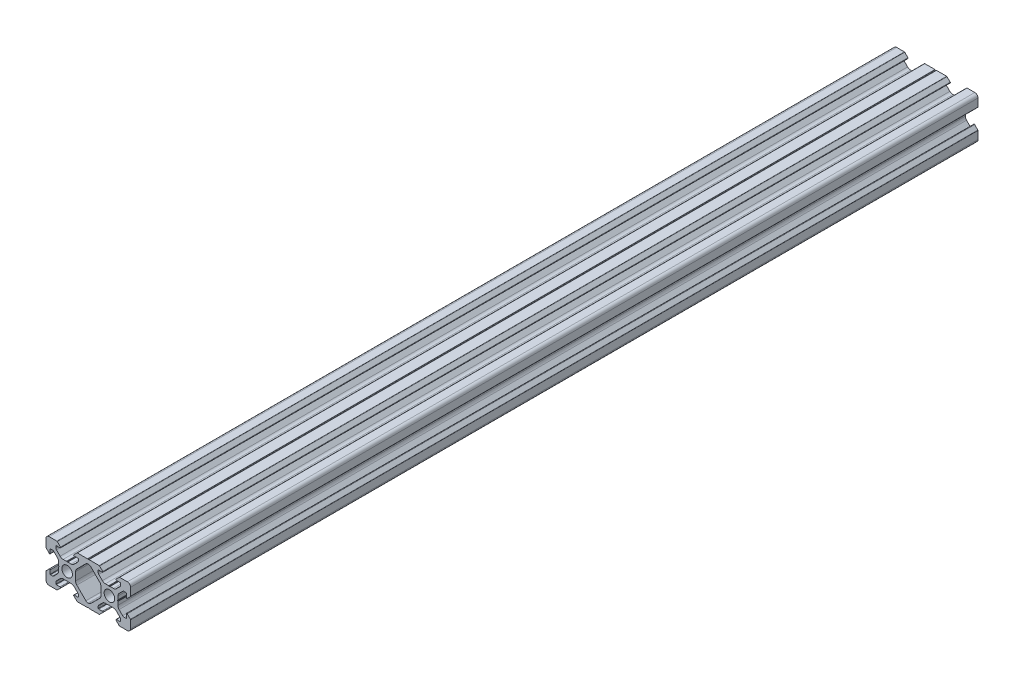
SolidWorks part; units mm, degrees
material "6063-T5"
ref_plane "Спереди" through (0, 0, 0) normal (0, 0, 1) x (1, 0, 0)
ref_plane "Сверху" through (0, 0, 0) normal (0, 1, 0) x (1, 0, 0)
ref_plane "Справа" through (0, 0, 0) normal (1, 0, 0) x (0, 0, -1)
sketch "Model" plane through (0, 0, 0) normal (0, 0, 1) x (1, 0, 0)
  line L0 (-5.4142, 2.9753) -> (-1.1373, 7.2523)
  line L1 (-6, -2.2365) -> (-6, 1.5611)
  line L2 (-5.4142, -3.6507) -> (-1.1373, -7.9276)
  line L3 (-0.1473, -8.3377) -> (0.1473, -8.3377)
  line L4 (5.4142, -3.6507) -> (1.1373, -7.9276)
  line L5 (6, -2.2365) -> (6, 1.5611)
  line L6 (5.4142, 2.9753) -> (1.1373, 7.2523)
  line L7 (-0.1473, 7.6623) -> (0.1473, 7.6623)
  line L8 (0.3757, 9.6623) -> (5.17, 9.6623)
  line L9 (5.3468, 9.5891) -> (6.8468, 8.0891)
  line L10 (6.67, 7.6623) -> (4.9, 7.6623)
  line L11 (4.7, 7.4623) -> (4.7, 6.6493)
  line L12 (4.9929, 5.9422) -> (6.687, 4.2481)
  line L13 (8.1012, 3.6623) -> (9.6623, 3.6623)
  line L14 (9.8185, 3.6075) -> (10, 3.4623)
  line L15 (10.1815, 3.6075) -> (10, 3.4623)
  line L16 (13.313, 4.2481) -> (15.0071, 5.9422)
  line L17 (15.3, 6.6493) -> (15.3, 7.4623)
  line L18 (15.1, 7.6623) -> (13.33, 7.6623)
  line L19 (14.6532, 9.5891) -> (13.1532, 8.0891)
  line L20 (14.83, 9.6623) -> (18.5, 9.6623)
  line L21 (20, 4.4923) -> (20, 8.1623)
  line L22 (19.9268, 4.3155) -> (18.4268, 2.8155)
  line L23 (18, 4.7623) -> (18, 2.9923)
  line L24 (16.987, 4.9623) -> (17.8, 4.9623)
  line L25 (14.5858, 2.9753) -> (16.2799, 4.6694)
  line L26 (14, 0) -> (14, 1.5611)
  line L27 (13.9452, -0.1562) -> (13.8, -0.3377)
  line L28 (13.9452, -0.5192) -> (13.8, -0.3377)
  line L29 (14, -0.6754) -> (14, -2.2365)
  line L30 (14.5858, -3.6507) -> (16.2799, -5.3448)
  line L31 (16.987, -5.6377) -> (17.8, -5.6377)
  line L32 (18, -5.4377) -> (18, -3.6677)
  line L33 (19.9268, -4.9909) -> (18.4268, -3.4909)
  line L34 (20, -5.1677) -> (20, -8.8377)
  line L35 (14.83, -10.3377) -> (18.5, -10.3377)
  line L36 (14.6532, -10.2645) -> (13.1532, -8.7645)
  line L37 (15.1, -8.3377) -> (13.33, -8.3377)
  line L38 (15.3, -7.3247) -> (15.3, -8.1377)
  line L39 (13.313, -4.9235) -> (15.0071, -6.6176)
  line L40 (10.3377, -4.3377) -> (11.8988, -4.3377)
  line L41 (10.1815, -4.2829) -> (10, -4.1377)
  line L42 (9.8185, -4.2829) -> (10, -4.1377)
  line L43 (8.1012, -4.3377) -> (9.6623, -4.3377)
  line L44 (4.9929, -6.6176) -> (6.687, -4.9235)
  line L45 (4.7, -8.1377) -> (4.7, -7.3247)
  line L46 (6.67, -8.3377) -> (4.9, -8.3377)
  line L47 (5.3468, -10.2645) -> (6.8468, -8.7645)
  line L48 (0.3757, -10.3377) -> (5.17, -10.3377)
  line L49 (0, -10.1377) -> (0.237, -10.2957)
  line L50 (0, -10.1377) -> (-0.237, -10.2957)
  line L51 (-0.3757, -10.3377) -> (-5.17, -10.3377)
  line L52 (-5.3468, -10.2645) -> (-6.8468, -8.7645)
  line L53 (-6.67, -8.3377) -> (-4.9, -8.3377)
  line L54 (-4.7, -8.1377) -> (-4.7, -7.3247)
  line L55 (-4.9929, -6.6176) -> (-6.687, -4.9235)
  line L56 (-8.1012, -4.3377) -> (-9.6623, -4.3377)
  line L57 (-9.8185, -4.2829) -> (-10, -4.1377)
  line L58 (-10.1815, -4.2829) -> (-10, -4.1377)
  line L59 (-10.3377, -4.3377) -> (-11.8988, -4.3377)
  line L60 (-13.313, -4.9235) -> (-15.0071, -6.6176)
  line L61 (-15.3, -7.3247) -> (-15.3, -8.1377)
  line L62 (-15.1, -8.3377) -> (-13.33, -8.3377)
  line L63 (-14.6532, -10.2645) -> (-13.1532, -8.7645)
  line L64 (-14.83, -10.3377) -> (-18.5, -10.3377)
  line L65 (-20, -5.1677) -> (-20, -8.8377)
  line L66 (-19.9268, -4.9909) -> (-18.4268, -3.4909)
  line L67 (-18, -5.4377) -> (-18, -3.6677)
  line L68 (-16.987, -5.6377) -> (-17.8, -5.6377)
  line L69 (-14.5858, -3.6507) -> (-16.2799, -5.3448)
  line L70 (-14, -0.6754) -> (-14, -2.2365)
  line L71 (-13.9452, -0.5192) -> (-13.8, -0.3377)
  line L72 (-13.9452, -0.1562) -> (-13.8, -0.3377)
  line L73 (-14, 0) -> (-14, 1.5611)
  line L74 (-14.5858, 2.9753) -> (-16.2799, 4.6694)
  line L75 (-16.987, 4.9623) -> (-17.8, 4.9623)
  line L76 (-18, 4.7623) -> (-18, 2.9923)
  line L77 (-19.9268, 4.3155) -> (-18.4268, 2.8155)
  line L78 (-20, 4.4923) -> (-20, 8.1623)
  line L79 (-14.6532, 9.5891) -> (-13.1532, 8.0891)
  line L80 (-10.1815, 3.6075) -> (-10, 3.4623)
  line L81 (-9.8185, 3.6075) -> (-10, 3.4623)
  line L82 (-8.1012, 3.6623) -> (-9.6623, 3.6623)
  line L83 (-4.9929, 5.9422) -> (-6.687, 4.2481)
  line L84 (-4.7, 7.4623) -> (-4.7, 6.6493)
  line L85 (-6.67, 7.6623) -> (-4.9, 7.6623)
  line L86 (-5.3468, 9.5891) -> (-6.8468, 8.0891)
  line L87 (-0.3757, 9.6623) -> (-5.17, 9.6623)
  line L88 (0, 9.4623) -> (-0.237, 9.6203)
  line L89 (0, 9.4623) -> (0.237, 9.6203)
  line L90 (10.3377, 3.6623) -> (11.8988, 3.6623)
  line L91 (-10.3377, 3.6623) -> (-11.8988, 3.6623)
  line L92 (-13.313, 4.2481) -> (-15.0071, 5.9422)
  line L93 (-15.3, 6.6493) -> (-15.3, 7.4623)
  line L94 (-15.1, 7.6623) -> (-13.33, 7.6623)
  line L95 (-14.83, 9.6623) -> (-18.5, 9.6623)
  circle A0 centre (10, -0.3377) radius 2.5
  arc A1 (-0.1473, 7.6623) -> (-1.1373, 7.2523) centre (-0.1473, 6.2623) ccw
  arc A2 (-5.4142, 2.9753) -> (-6, 1.5611) centre (-4, 1.5611) ccw
  arc A3 (-6, -2.2365) -> (-5.4142, -3.6507) centre (-4, -2.2365) ccw
  arc A4 (-1.1373, -7.9276) -> (-0.1473, -8.3377) centre (-0.1473, -6.9377) ccw
  arc A5 (0.1473, -8.3377) -> (1.1373, -7.9276) centre (0.1473, -6.9377) ccw
  arc A6 (5.4142, -3.6507) -> (6, -2.2365) centre (4, -2.2365) ccw
  arc A7 (6, 1.5611) -> (5.4142, 2.9753) centre (4, 1.5611) ccw
  arc A8 (1.1373, 7.2523) -> (0.1473, 7.6623) centre (0.1473, 6.2623) ccw
  arc A9 (0.3757, 9.6623) -> (0.237, 9.6203) centre (0.3757, 9.4123) ccw
  arc A10 (5.3468, 9.5891) -> (5.17, 9.6623) centre (5.17, 9.4123) ccw
  arc A11 (6.67, 7.6623) -> (6.8468, 8.0891) centre (6.67, 7.9123) ccw
  arc A12 (4.9, 7.6623) -> (4.7, 7.4623) centre (4.9, 7.4623) ccw
  arc A13 (4.7, 6.6493) -> (4.9929, 5.9422) centre (5.7, 6.6493) ccw
  arc A14 (6.687, 4.2481) -> (8.1012, 3.6623) centre (8.1012, 5.6623) ccw
  arc A15 (9.8185, 3.6075) -> (9.6623, 3.6623) centre (9.6623, 3.4123) ccw
  arc A16 (10.3377, 3.6623) -> (10.1815, 3.6075) centre (10.3377, 3.4123) ccw
  arc A17 (11.8988, 3.6623) -> (13.313, 4.2481) centre (11.8988, 5.6623) ccw
  arc A18 (15.0071, 5.9422) -> (15.3, 6.6493) centre (14.3, 6.6493) ccw
  arc A19 (15.3, 7.4623) -> (15.1, 7.6623) centre (15.1, 7.4623) ccw
  arc A20 (13.1532, 8.0891) -> (13.33, 7.6623) centre (13.33, 7.9123) ccw
  arc A21 (14.83, 9.6623) -> (14.6532, 9.5891) centre (14.83, 9.4123) ccw
  arc A22 (20, 8.1623) -> (18.5, 9.6623) centre (18.5, 8.1623) ccw
  arc A23 (19.9268, 4.3155) -> (20, 4.4923) centre (19.75, 4.4923) ccw
  arc A24 (18, 2.9923) -> (18.4268, 2.8155) centre (18.25, 2.9923) ccw
  arc A25 (18, 4.7623) -> (17.8, 4.9623) centre (17.8, 4.7623) ccw
  arc A26 (16.987, 4.9623) -> (16.2799, 4.6694) centre (16.987, 3.9623) ccw
  arc A27 (14.5858, 2.9753) -> (14, 1.5611) centre (16, 1.5611) ccw
  arc A28 (13.9452, -0.1562) -> (14, 0) centre (13.75, 0) ccw
  arc A29 (14, -0.6754) -> (13.9452, -0.5192) centre (13.75, -0.6754) ccw
  arc A30 (14, -2.2365) -> (14.5858, -3.6507) centre (16, -2.2365) ccw
  arc A31 (16.2799, -5.3448) -> (16.987, -5.6377) centre (16.987, -4.6377) ccw
  arc A32 (17.8, -5.6377) -> (18, -5.4377) centre (17.8, -5.4377) ccw
  arc A33 (18.4268, -3.4909) -> (18, -3.6677) centre (18.25, -3.6677) ccw
  arc A34 (20, -5.1677) -> (19.9268, -4.9909) centre (19.75, -5.1677) ccw
  arc A35 (18.5, -10.3377) -> (20, -8.8377) centre (18.5, -8.8377) ccw
  arc A36 (14.6532, -10.2645) -> (14.83, -10.3377) centre (14.83, -10.0877) ccw
  arc A37 (13.33, -8.3377) -> (13.1532, -8.7645) centre (13.33, -8.5877) ccw
  arc A38 (15.1, -8.3377) -> (15.3, -8.1377) centre (15.1, -8.1377) ccw
  arc A39 (15.3, -7.3247) -> (15.0071, -6.6176) centre (14.3, -7.3247) ccw
  arc A40 (13.313, -4.9235) -> (11.8988, -4.3377) centre (11.8988, -6.3377) ccw
  arc A41 (10.1815, -4.2829) -> (10.3377, -4.3377) centre (10.3377, -4.0877) ccw
  arc A42 (9.6623, -4.3377) -> (9.8185, -4.2829) centre (9.6623, -4.0877) ccw
  arc A43 (8.1012, -4.3377) -> (6.687, -4.9235) centre (8.1012, -6.3377) ccw
  arc A44 (4.9929, -6.6176) -> (4.7, -7.3247) centre (5.7, -7.3247) ccw
  arc A45 (4.7, -8.1377) -> (4.9, -8.3377) centre (4.9, -8.1377) ccw
  arc A46 (6.8468, -8.7645) -> (6.67, -8.3377) centre (6.67, -8.5877) ccw
  arc A47 (5.17, -10.3377) -> (5.3468, -10.2645) centre (5.17, -10.0877) ccw
  arc A48 (0.237, -10.2957) -> (0.3757, -10.3377) centre (0.3757, -10.0877) ccw
  arc A49 (-0.3757, -10.3377) -> (-0.237, -10.2957) centre (-0.3757, -10.0877) ccw
  arc A50 (-5.3468, -10.2645) -> (-5.17, -10.3377) centre (-5.17, -10.0877) ccw
  arc A51 (-6.67, -8.3377) -> (-6.8468, -8.7645) centre (-6.67, -8.5877) ccw
  arc A52 (-4.9, -8.3377) -> (-4.7, -8.1377) centre (-4.9, -8.1377) ccw
  arc A53 (-4.7, -7.3247) -> (-4.9929, -6.6176) centre (-5.7, -7.3247) ccw
  arc A54 (-6.687, -4.9235) -> (-8.1012, -4.3377) centre (-8.1012, -6.3377) ccw
  arc A55 (-9.8185, -4.2829) -> (-9.6623, -4.3377) centre (-9.6623, -4.0877) ccw
  arc A56 (-10.3377, -4.3377) -> (-10.1815, -4.2829) centre (-10.3377, -4.0877) ccw
  arc A57 (-11.8988, -4.3377) -> (-13.313, -4.9235) centre (-11.8988, -6.3377) ccw
  arc A58 (-15.0071, -6.6176) -> (-15.3, -7.3247) centre (-14.3, -7.3247) ccw
  arc A59 (-15.3, -8.1377) -> (-15.1, -8.3377) centre (-15.1, -8.1377) ccw
  arc A60 (-13.1532, -8.7645) -> (-13.33, -8.3377) centre (-13.33, -8.5877) ccw
  arc A61 (-14.83, -10.3377) -> (-14.6532, -10.2645) centre (-14.83, -10.0877) ccw
  arc A62 (-20, -8.8377) -> (-18.5, -10.3377) centre (-18.5, -8.8377) ccw
  arc A63 (-19.9268, -4.9909) -> (-20, -5.1677) centre (-19.75, -5.1677) ccw
  arc A64 (-18, -3.6677) -> (-18.4268, -3.4909) centre (-18.25, -3.6677) ccw
  arc A65 (-18, -5.4377) -> (-17.8, -5.6377) centre (-17.8, -5.4377) ccw
  arc A66 (-16.987, -5.6377) -> (-16.2799, -5.3448) centre (-16.987, -4.6377) ccw
  arc A67 (-14.5858, -3.6507) -> (-14, -2.2365) centre (-16, -2.2365) ccw
  arc A68 (-13.9452, -0.5192) -> (-14, -0.6754) centre (-13.75, -0.6754) ccw
  arc A69 (-14, 0) -> (-13.9452, -0.1562) centre (-13.75, 0) ccw
  arc A70 (-14, 1.5611) -> (-14.5858, 2.9753) centre (-16, 1.5611) ccw
  arc A71 (-16.2799, 4.6694) -> (-16.987, 4.9623) centre (-16.987, 3.9623) ccw
  arc A72 (-17.8, 4.9623) -> (-18, 4.7623) centre (-17.8, 4.7623) ccw
  arc A73 (-18.4268, 2.8155) -> (-18, 2.9923) centre (-18.25, 2.9923) ccw
  arc A74 (-20, 4.4923) -> (-19.9268, 4.3155) centre (-19.75, 4.4923) ccw
  arc A75 (-18.5, 9.6623) -> (-20, 8.1623) centre (-18.5, 8.1623) ccw
  arc A76 (-14.6532, 9.5891) -> (-14.83, 9.6623) centre (-14.83, 9.4123) ccw
  arc A77 (-13.33, 7.6623) -> (-13.1532, 8.0891) centre (-13.33, 7.9123) ccw
  arc A78 (-15.1, 7.6623) -> (-15.3, 7.4623) centre (-15.1, 7.4623) ccw
  arc A79 (-15.3, 6.6493) -> (-15.0071, 5.9422) centre (-14.3, 6.6493) ccw
  arc A80 (-13.313, 4.2481) -> (-11.8988, 3.6623) centre (-11.8988, 5.6623) ccw
  arc A81 (-10.1815, 3.6075) -> (-10.3377, 3.6623) centre (-10.3377, 3.4123) ccw
  arc A82 (-9.6623, 3.6623) -> (-9.8185, 3.6075) centre (-9.6623, 3.4123) ccw
  arc A83 (-8.1012, 3.6623) -> (-6.687, 4.2481) centre (-8.1012, 5.6623) ccw
  arc A84 (-4.9929, 5.9422) -> (-4.7, 6.6493) centre (-5.7, 6.6493) ccw
  arc A85 (-4.7, 7.4623) -> (-4.9, 7.6623) centre (-4.9, 7.4623) ccw
  arc A86 (-6.8468, 8.0891) -> (-6.67, 7.6623) centre (-6.67, 7.9123) ccw
  arc A87 (-5.17, 9.6623) -> (-5.3468, 9.5891) centre (-5.17, 9.4123) ccw
  arc A88 (-0.237, 9.6203) -> (-0.3757, 9.6623) centre (-0.3757, 9.4123) ccw
  circle A89 centre (-10, -0.3377) radius 2.5
  dimension "D1" = 20
extrude "Body" add sketch "Model" along normal blind 401
cosmetic thread "Условное изображение резьбы1" parameters "D1"=15, "D2"=6
cosmetic thread "Условное изображение резьбы2" parameters "D1"=15, "D2"=6
cosmetic thread "Условное изображение резьбы3" parameters "D1"=15, "D2"=6
cosmetic thread "Условное изображение резьбы4" parameters "D1"=15, "D2"=6
